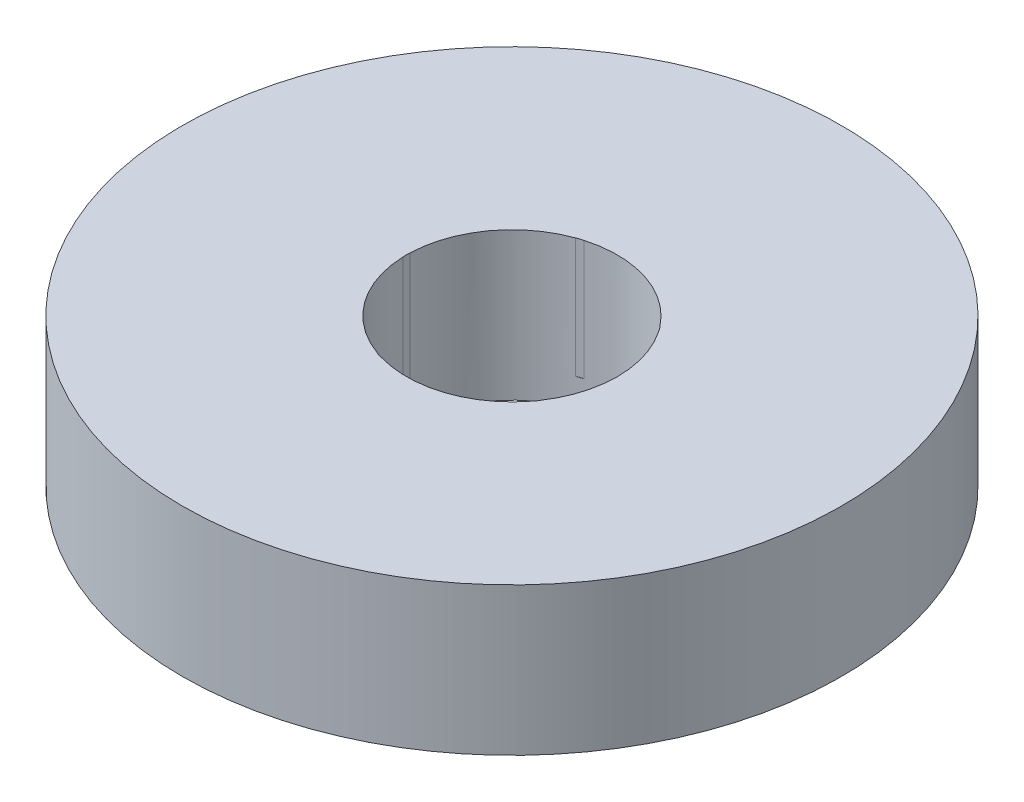
SolidWorks part; units mm, degrees
ref_plane "Front Plane" through (0, 0, 0) normal (0, 0, 1) x (1, 0, 0)
ref_plane "Top Plane" through (0, 0, 0) normal (0, 1, 0) x (1, 0, 0)
ref_plane "Right Plane" through (0, 0, 0) normal (1, 0, 0) x (0, 0, -1)
sketch "Sketch1" plane through (0, 0, 0) normal (0, 1, 0) x (1, 0, 0)
  circle A0 centre (0, 0) radius 62.5
  dimension "FLANGE_OD" = 125
extrude "Boss-Extrude1" add sketch "Sketch1" along normal blind 28
sketch "Sketch2" plane through (0, 0, 0) normal (0, 1, 0) x (1, 0, 0)
  circle A0 centre (0, 0) radius 20
  dimension "BORE_D" = 40
extrude "Cut-Extrude1" cut sketch "Sketch2" along normal through all
sketch "Sketch3" plane through (0, 28, 0) normal (0, 1, 0) x (1, 0, 0)
  circle A0 centre (0, 0) radius 15.2415 construction
  circle A1 centre (-15.2415, 0) radius 4.7922
  dimension "BOLT_D" = 9.5844
  dimension "BOLT_PCD" = 30.483
extrude "Cut-Extrude2" cut sketch "Sketch3" against normal blind 22.7356
pattern_circular "CirPattern1" count 5 over 360 about axis through (0, 0, 0) along (0, 1, 0) of "Cut-Extrude2"
